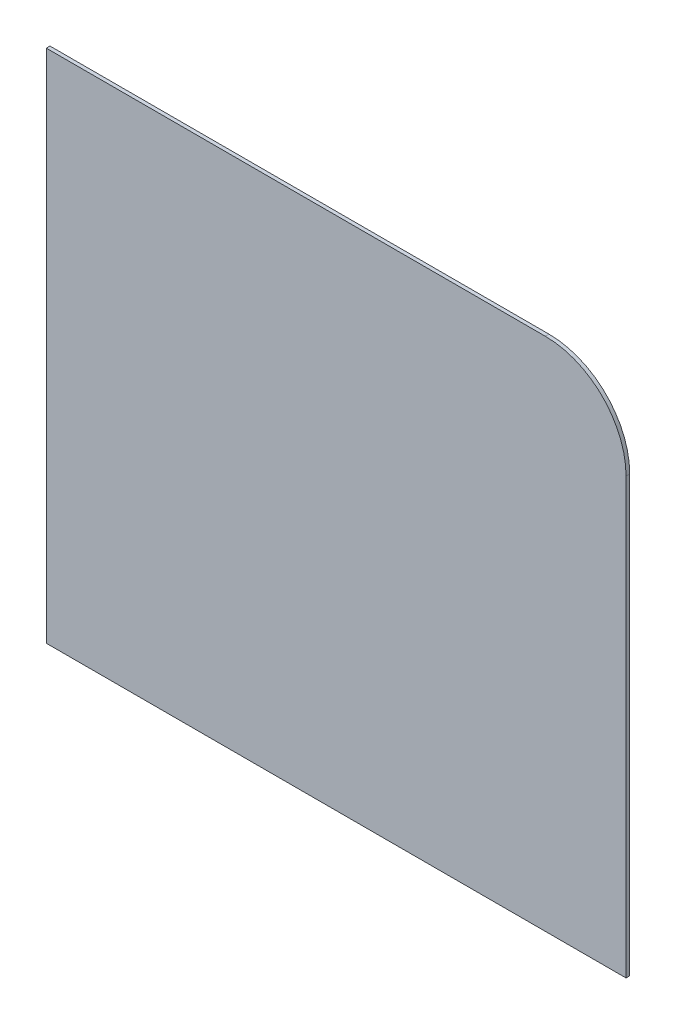
SolidWorks part; units mm, degrees
ref_plane "Front Plane" through (0, 0, 0) normal (0, 0, 1) x (1, 0, 0)
ref_plane "Top Plane" through (0, 0, 0) normal (0, 1, 0) x (1, 0, 0)
ref_plane "Right Plane" through (0, 0, 0) normal (1, 0, 0) x (0, 0, -1)
sketch "Sketch1" plane through (0, 0, 0) normal (0, 0, 1) x (1, 0, 0)
  line L0 (195, 450) -> (-195, 450) construction
  line L1 (265, 450) -> (-237.6309, 450)
  line L2 (265, 450) -> (265, 3.2)
  line L3 (265, 3.2) -> (-237.6309, 3.2)
  line L4 (-237.6309, 450) -> (-237.6309, 3.2)
  line L5 (265, 380) -> (265, 0) construction
  line L7 (265, 3.2) -> (-195, 3.2) construction
extrude "Boss-Extrude1" add sketch "Sketch1" along normal blind 3.175 from offset 500 contours L4 L3 L2 L1
fillet "Fillet1" radius 70 1 edges at (265, 450, 501.5875)
